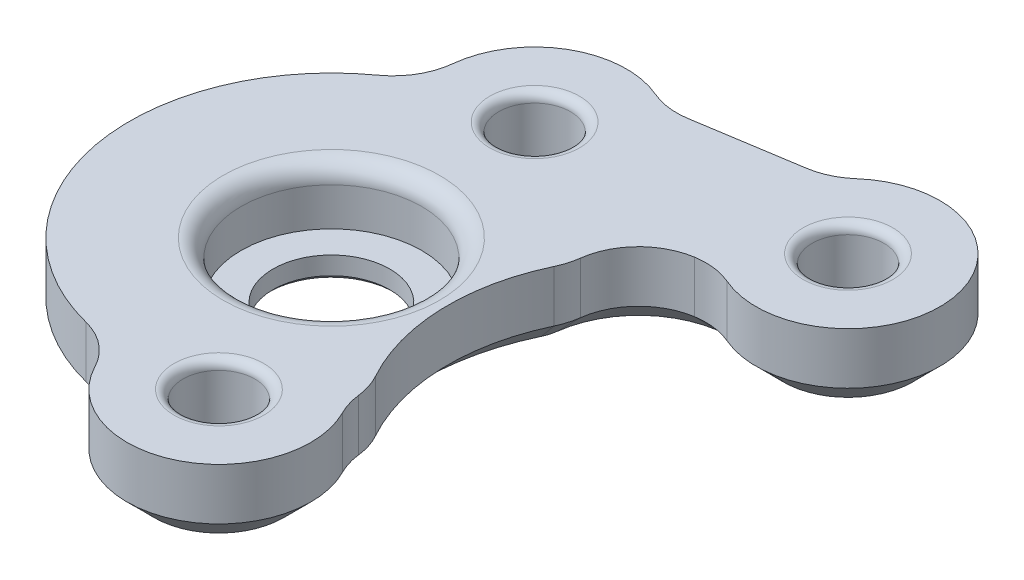
SolidWorks part; units mm, degrees
ref_plane "Front Plane" through (0, 0, 0) normal (0, 0, 1) x (1, 0, 0)
ref_plane "Top Plane" through (0, 0, 0) normal (0, 1, 0) x (1, 0, 0)
ref_plane "Right Plane" through (0, 0, 0) normal (1, 0, 0) x (0, 0, -1)
sketch "Sketch1" plane through (0, 0, 0) normal (0, 1, 0) x (1, 0, 0)
  circle A0 centre (0, 0) radius 9
  circle A1 centre (0, 0) radius 4.025
  dimension "D1" = 18
  dimension "D2" = 8.05
extrude "Boss-Extrude1" add sketch "Sketch1" along normal blind 3.5
sketch "Sketch2" plane through (0, 3.5, 0) normal (0, 1, 0) x (1, 0, 0)
  circle A0 centre (3.3433, -8.356) radius 1.6
  circle A1 centre (0.0612, 8.9998) radius 1.6
  circle A2 centre (3.3433, -8.356) radius 4.1
  circle A3 centre (0.0612, 8.9998) radius 4.1
  dimension "D1" = 2.5
extrude "Boss-Extrude2" add sketch "Sketch2" against normal blind 3.5
sketch "Sketch6" plane through (0, 0, 0) normal (0, -1, 0) x (-1, 0, 0)
  circle A0 centre (-14.2, 0) radius 9
  dimension "D1" = 18
  dimension "D2" = 14.2
extrude "Cut-Extrude2" cut sketch "Sketch6" against normal through all
sketch "Sketch3" plane through (0, 0, 0) normal (0, -1, 0) x (-1, 0, 0)
  circle A0 centre (-0.0612, 8.9998) radius 1.6
  arc A1 (-4.7701, -7.6319) -> (-1.8108, -8.8159) centre (0, 0) ccw construction
  arc A2 (1.5334, 8.8684) -> (-1.6538, 8.8467) centre (0, 0) ccw construction
  circle A4 centre (-3.3433, -8.356) radius 1.6
extrude "Cut-Extrude1" cut sketch "Sketch3" against normal blind 3.5
sketch "Sketch4" plane through (0, 0, 0) normal (0, -1, 0) x (-1, 0, 0)
  line L0 (-0.0612, 8.9998) -> (-12.1263, 10.9048) construction
  line L1 (-2.3537, 12.3989) -> (-8.898, 13.4322)
  line L3 (-5.8131, 6.8708) -> (-9.8338, 7.5057)
  circle A0 centre (-12.1263, 10.9048) radius 1.6
  arc A1 (-8.898, 13.4322) -> (-9.8338, 7.5057) centre (-12.1263, 10.9048) ccw
  arc A2 (-2.3537, 12.3989) -> (-4.047, 8.0388) centre (-0.0612, 8.9998) ccw
  arc A3 (-4.047, 8.0388) -> (-5.8131, 6.8708) centre (0, 0) ccw
  circle A5 centre (-12.1263, 10.9048) radius 4.1 construction
  point P4 (-12.1263, 10.9048)
  point P5 (-12.1263, 10.9048)
  point P8 (-7.2556, 11.7052)
  point P9 (-12.1263, 10.9048)
  point P10 (-8.0263, 10.9048)
  point P13 (-8.0263, 10.9048)
  point P17 (-8.0263, 10.9048)
  arc M5 (-4.047, 8.0388) -> (-7.1, 5.5308) centre (0, 0) ccw
  dimension "D2" = 3
  dimension "D1" = 2.5
extrude "Boss-Extrude3" add sketch "Sketch4" against normal blind 3.5 contours A0 M5 region at (9.8918, 0, -10.6162)
sketch "Sketch5" plane through (0, 0, 0) normal (0, -1, 0) x (-1, 0, 0)
  circle A0 centre (0, 0) radius 4.025
  circle A1 centre (0, 0) radius 2.6
  dimension "D1" = 5.2
extrude "Boss-Extrude4" add sketch "Sketch5" against normal blind 1
fillet "Fillet1" radius 3 7 edges at (-3.9373, 1.75, -8.0931) (-0.7102, 1.75, 8.9719) (9.8338, 1.75, -7.5057) (8.898, 1.75, -13.4322) (2.3537, 1.75, -12.3989) (7.1, 1.75, -5.5308) (7.1, 1.75, 5.5308)
fillet "Fillet9" radius 3 2 edges at (5.8131, 1.75, -6.8708) (6.7029, 1.75, 6.0059)
fillet "Fillet7" radius 0.8 1 edges at (0, 3.5, 4.025)
fillet "Fillet8" radius 0.4 3 edges at (3.3433, 3.5, 9.956) (12.1263, 3.5, -12.5048) (0.0612, 3.5, -7.3998)
chamfer "倒角1" distance 1.2 angle 45 16 edges at (16.1761, 0, -11.5442) (8.7151, 0, -13.5234) (9.6878, 0, -7.3626) (5.6259, 0, -12.9156) (8.8438, 0, -7.3493) (2.4996, 0, -12.542) (7.1582, 0, -6.4755) (-2.0077, 0, -12.5396) (6.238, 0, -4.3017) (-4.406, 0, -8.2391) (5.2046, 0, 0.2865) (-8.8433, 0, 1.6723) (6.5641, 0, 4.9054) (-1.0932, 0, 9.279) (6.7966, 0, 5.9989) (5.2201, 0, 12.0012)
chamfer "倒角2" distance 0.2 angle 45 4 edges at (3.3433, 0, 9.956) (12.1263, 0, -12.5048) (0, 0, -2.6) (0.0612, 0, -7.3998)
equation "\"D2@Sketch6\"=5.2+\"D1@Sketch6\"/2"
